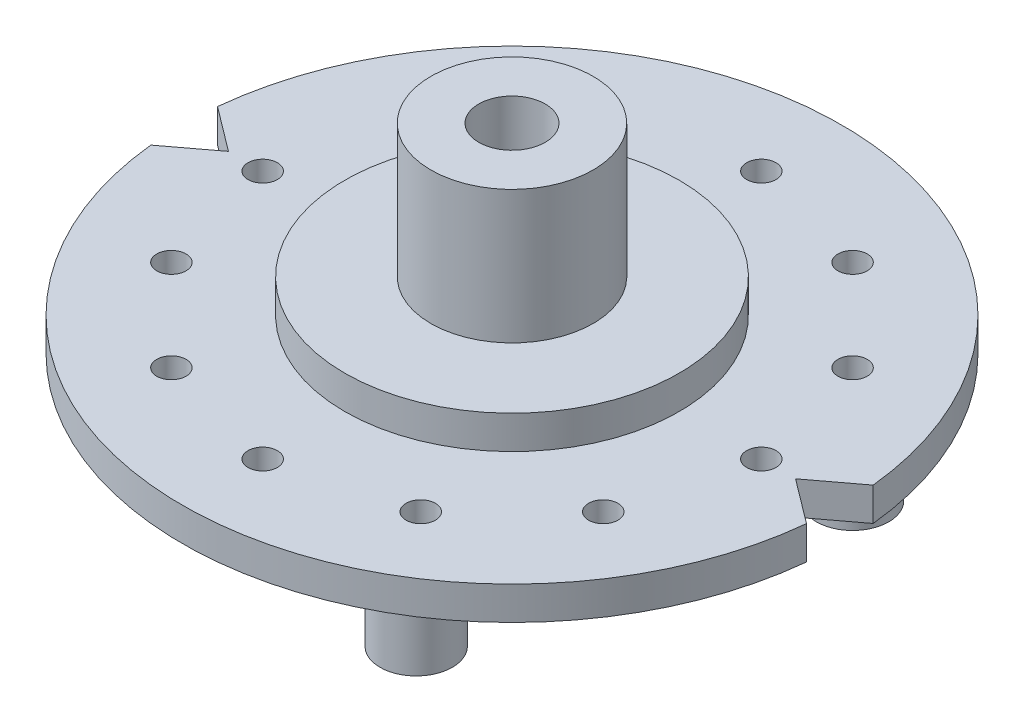
SolidWorks part; units mm, degrees
note: The reader was unsure of these and kept them because the rebuilt part matched: shared geometry of "Croquis1<3>", "Croquis1<4>".
ref_plane "Alzado" through (0, 0, 0) normal (0, 0, 1) x (1, 0, 0)
ref_plane "Planta" through (0, 0, 0) normal (0, 1, 0) x (1, 0, 0)
ref_plane "Vista lateral" through (0, 0, 0) normal (1, 0, 0) x (0, 0, -1)
sketch "Croquis1" plane through (0, 0, 0) normal (0, 1, 0) x (1, 0, 0)
  line L0 (0, 0) -> (79.3406, 0) construction
  line L1 (0, 0) -> (0, 56.2157) construction
  line L2 (0, 0) -> (78.5647, -45.3594) construction
  line L3 (36.83, 0) -> (42.5792, 4.3323)
  line L4 (36.83, 0) -> (42.5792, -4.3323)
  line L5 (-36.83, 0) -> (-42.5792, -4.3323)
  line L6 (-36.83, 0) -> (-42.5792, 4.3323)
  arc A0 (42.5792, 4.3323) -> (-42.5792, 4.3323) centre (0, 0) ccw
  circle A1 centre (0, 0) radius 36.83 construction
  circle A2 centre (0, 0) radius 32.385 construction
  arc A3 (-42.5792, -4.3323) -> (42.5792, -4.3323) centre (0, 0) ccw
  circle A4 centre (0, 0) radius 10.541
  circle A5 centre (0, 0) radius 21.717
  circle A6 centre (28.0462, -16.1925) radius 1.905
  circle A7 centre (16.1925, -28.0462) radius 1.905
  circle A8 centre (0, -32.385) radius 1.905
  circle A9 centre (-16.1925, -28.0462) radius 1.905
  circle A10 centre (-28.0462, -16.1925) radius 1.905
  circle A11 centre (-32.385, 0) radius 1.905
  circle A12 centre (-28.0462, 16.1925) radius 1.905
  circle A13 centre (-16.1925, 28.0462) radius 1.905
  circle A14 centre (0, 32.385) radius 1.905
  circle A15 centre (16.1925, 28.0462) radius 1.905
  circle A16 centre (28.0462, 16.1925) radius 1.905
  circle A17 centre (32.385, 0) radius 1.905
  point P41 (0, 0)
  dimension "D1" = 85.598
  dimension "D2" = 73.66
  dimension "D3" = 64.77
  dimension "D7" = 43.434
  dimension "D8" = 21.082
  dimension "D9" = 3.81
  dimension "D4" = 30
  dimension "D5" = 74
  dimension "D6" = 37
  dimension "D10" = 12
extrude "Saliente-Extruir1" add sketch "Croquis1" along normal blind 4.318 contours L5 A3 L4 L3 A0 L6 A17 A16 A15 A14 A13 A12 A11 A10 A9 A8 A7 A6 A5
extrude "Saliente-Extruir2" add sketch "Croquis1<3>" along normal blind 8.636 contours A5 A4
sketch "Croquis1<3>" plane through (0, 0, 0) normal (0, 1, 0) x (1, 0, 0) same geometry as "Croquis1"
extrude "Saliente-Extruir3" add sketch "Croquis1<4>" along normal blind 25.908 contours A4
sketch "Croquis1<4>" plane through (0, 0, 0) normal (0, 1, 0) x (1, 0, 0) same geometry as "Croquis1"
hole_wizard "Taladro1" positions "Croquis2" profile "Croquis4" legacy
sketch "Croquis2" plane through (0, 25.908, 0) normal (0, 1, 0) x (1, 0, 0)
  point P0 (0, 0)
sketch "Croquis4" plane through (0, 25.908, 0) normal (1, 0, 0) x (0, 0, 1)
  line L0 (0, 0) -> (0, 21.59)
  line L1 (0, 21.59) -> (4.318, 21.59)
  line L2 (4.318, 21.59) -> (4.318, 0)
  line L3 (4.318, 0) -> (0, 0)
  line L4 (0, 110) -> (0, -10) construction
  dimension "Diámetro" = 8.636
  dimension "Profundidad" = 21.59
sketch "Croquis5" plane through (0, 0, 0) normal (0, -1, 0) x (1, 0, 0)
  line L0 (0, 0) -> (51.5603, 0) construction
  line L1 (0, 0) -> (46.3982, -26.788) construction
  circle A0 centre (0, 0) radius 32.385 construction
  circle A1 centre (28.0462, -16.1925) radius 4.699
  point P7 (0, 0)
  dimension "D1" = 30
  dimension "D2" = 64.77
  dimension "D3" = 9.398
extrude "Saliente-Extruir4" add sketch "Croquis5" along normal blind 10.668
pattern_circular "MatrizC1" count 4 over 360 about axis through (-0.2952, 0, 0.1704) along (0, 1, 0) of "Saliente-Extruir4"
